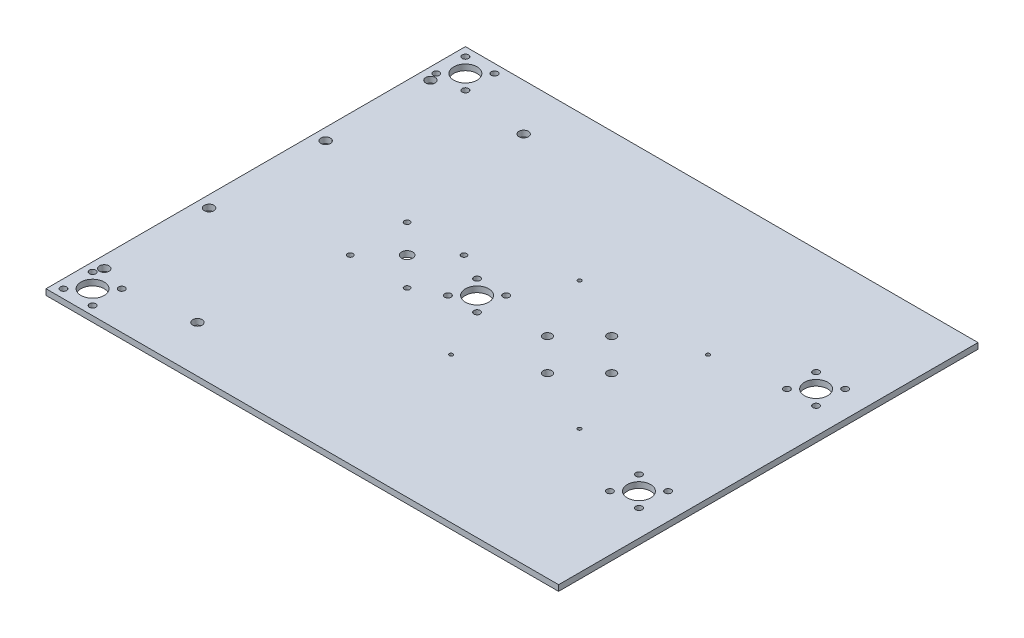
SolidWorks part; units mm, degrees
ref_plane "Front Plane" through (0, 0, 0) normal (0, 0, 1) x (1, 0, 0)
ref_plane "Top Plane" through (0, 0, 0) normal (0, 1, 0) x (1, 0, 0)
ref_plane "Right Plane" through (0, 0, 0) normal (1, 0, 0) x (0, 0, -1)
sketch "Sketch1" plane through (0, 0, 0) normal (0, 1, 0) x (1, 0, 0)
  line L1 (-139.7, -114.3) -> (139.7, -114.3)
  line L2 (-139.7, -114.3) -> (-139.7, 114.3)
  line L3 (-139.7, 114.3) -> (139.7, 114.3)
  line L4 (139.7, -114.3) -> (139.7, 114.3)
  line L5 (-139.7, -114.3) -> (139.7, 114.3) construction
  line L6 (-139.7, 114.3) -> (139.7, -114.3) construction
  point P0 (0, 0)
  dimension "D1" = 228.6
  dimension "D2" = 279.4
extrude "Boss-Extrude1" add sketch "Sketch1" along normal blind 3.175
sketch "Sketch2" plane through (0, 0, 0) normal (0, 1, 0) x (1, 0, 0)
  line L0 (-193.2668, 0) -> (192.9727, 0) construction
sketch "Sketch3" plane through (0, 3.175, 0) normal (0, 1, 0) x (1, 0, 0)
  circle A1 centre (-133.35, -31.75) radius 2.6
  circle A2 centre (-133.35, -31.75) radius 2.6
  circle A3 centre (-82.55, -88.9) radius 2.6
  circle A4 centre (-82.55, -88.9) radius 2.6
  circle A5 centre (-133.35, -88.9) radius 2.6
  circle A6 centre (-133.35, -88.9) radius 2.6
  dimension "D1" = 0
  dimension "D2" = 0
  dimension "D3" = 0
sketch "Sketch5" plane through (0, 3.175, 0) normal (0, 1, 0) x (1, 0, 0)
  circle A0 centre (-41.674, 15.5) radius 1.5 construction
  circle A1 centre (-41.674, -15.5) radius 1.5 construction
  circle A2 centre (-72.674, 15.5) radius 1.5 construction
  circle A3 centre (-72.674, -15.5) radius 1.5 construction
  circle A4 centre (-57.174, 0) radius 2.5 construction
  circle A5 centre (-41.674, 15.5) radius 1.5
  circle A6 centre (-41.674, -15.5) radius 1.5
  circle A7 centre (-72.674, 15.5) radius 1.5
  circle A8 centre (-72.674, -15.5) radius 1.5
  circle A9 centre (-57.174, 0) radius 2.5 construction
  circle A10 centre (-57.174, 0) radius 3.008
  dimension "D1" = 6.016
sketch "Sketch7" plane through (0, 3.175, 0) normal (0, 1, 0) x (1, 0, 0)
  circle A0 centre (71.8318, -35.0018) radius 1 construction
  circle A1 centre (1.8282, -35.0018) radius 1 construction
  circle A2 centre (71.8318, -35.0018) radius 1
  circle A3 centre (1.8282, -35.0018) radius 1
  circle A4 centre (1.8282, 35.0018) radius 1 construction
  circle A5 centre (71.8318, 35.0018) radius 1 construction
  circle A6 centre (1.8282, 35.0018) radius 1
  circle A7 centre (71.8318, 35.0018) radius 1
extrude "Cut-Extrude1" cut sketch "Sketch3" against normal through all
mirror "Mirror1" about plane through (0, 0, 0) normal (0, 0, 1) of "Cut-Extrude1"
extrude "Cut-Extrude2" cut sketch "Sketch5" against normal through all
extrude "Cut-Extrude3" cut sketch "Sketch7" against normal through all
sketch "Sketch8" plane through (0, 3.175, 0) normal (0, 1, 0) x (1, 0, 0)
  arc A0 (36.83, -19.85) -> (36.83, -15.15) centre (36.83, -17.5) ccw construction
  arc A1 (36.83, -19.85) -> (36.83, -15.15) centre (36.83, -17.5) ccw
  arc A2 (36.83, -15.15) -> (36.83, -19.85) centre (36.83, -17.5) ccw construction
  arc A3 (36.83, -15.15) -> (36.83, -19.85) centre (36.83, -17.5) ccw
  circle A4 centre (19.33, 0) radius 2.35 construction
  circle A5 centre (19.33, 0) radius 2.35
  arc A6 (36.83, 15.15) -> (36.83, 19.85) centre (36.83, 17.5) ccw construction
  arc A7 (36.83, 15.15) -> (36.83, 19.85) centre (36.83, 17.5) ccw
  arc A8 (36.83, 19.85) -> (36.83, 15.15) centre (36.83, 17.5) ccw construction
  arc A9 (36.83, 19.85) -> (36.83, 15.15) centre (36.83, 17.5) ccw
  circle A10 centre (54.33, 0) radius 2.35 construction
  circle A11 centre (54.33, 0) radius 2.35
extrude "Cut-Extrude4" cut sketch "Sketch8" against normal through all
sketch "Sketch9" plane through (0, 3.175, 0) normal (0, 1, 0) x (1, 0, 0)
  circle A0 centre (-119.0625, -109.5375) radius 1.727 construction
  circle A1 centre (-119.0625, -93.6625) radius 1.727 construction
  circle A2 centre (-134.9375, -93.6625) radius 1.727 construction
  circle A3 centre (-134.9375, -109.5375) radius 1.727 construction
  circle A4 centre (-127, -101.6) radius 6.35 construction
  circle A5 centre (-119.0625, -109.5375) radius 1.727
  circle A6 centre (-119.0625, -93.6625) radius 1.727
  circle A7 centre (-134.9375, -93.6625) radius 1.727
  circle A8 centre (-134.9375, -109.5375) radius 1.727
  circle A9 centre (-127, -101.6) radius 6.35
  circle A10 centre (125.4125, -56.1975) radius 1.727 construction
  circle A11 centre (125.4125, -40.3225) radius 1.727 construction
  circle A12 centre (117.475, -48.26) radius 6.35 construction
  circle A13 centre (109.5375, -40.3225) radius 1.727 construction
  circle A14 centre (109.5375, -56.1975) radius 1.727 construction
  circle A15 centre (125.4125, -56.1975) radius 1.727
  circle A16 centre (125.4125, -40.3225) radius 1.727
  circle A17 centre (117.475, -48.26) radius 6.35
  circle A18 centre (109.5375, -40.3225) radius 1.727
  circle A19 centre (109.5375, -56.1975) radius 1.727
  circle A20 centre (-11.1125, 7.9375) radius 1.727 construction
  circle A21 centre (-11.1125, -7.9375) radius 1.727 construction
  circle A22 centre (-19.05, 0) radius 6.35 construction
  circle A23 centre (-26.9875, -7.9375) radius 1.727 construction
  circle A24 centre (-26.9875, 7.9375) radius 1.727 construction
  circle A25 centre (-11.1125, 7.9375) radius 1.727
  circle A26 centre (-11.1125, -7.9375) radius 1.727
  circle A27 centre (-19.05, 0) radius 6.35
  circle A28 centre (-26.9875, -7.9375) radius 1.727
  circle A29 centre (-26.9875, 7.9375) radius 1.727
  circle A30 centre (109.5375, 56.1975) radius 1.727 construction
  circle A31 centre (109.5375, 40.3225) radius 1.727 construction
  circle A32 centre (125.4125, 56.1975) radius 1.727 construction
  circle A33 centre (117.475, 48.26) radius 6.35 construction
  circle A34 centre (125.4125, 40.3225) radius 1.727 construction
  circle A35 centre (109.5375, 56.1975) radius 1.727
  circle A36 centre (109.5375, 40.3225) radius 1.727
  circle A37 centre (125.4125, 56.1975) radius 1.727
  circle A38 centre (117.475, 48.26) radius 6.35
  circle A39 centre (125.4125, 40.3225) radius 1.727
  circle A40 centre (-119.0625, 93.6625) radius 1.727 construction
  circle A41 centre (-119.0625, 109.5375) radius 1.727 construction
  circle A42 centre (-134.9375, 109.5375) radius 1.727 construction
  circle A43 centre (-134.9375, 93.6625) radius 1.727 construction
  circle A44 centre (-119.0625, 93.6625) radius 1.727
  circle A45 centre (-119.0625, 109.5375) radius 1.727
  circle A46 centre (-134.9375, 109.5375) radius 1.727
  circle A47 centre (-134.9375, 93.6625) radius 1.727
  circle A48 centre (-127, 101.6) radius 6.35 construction
  circle A49 centre (-127, 101.6) radius 6.35
extrude "Cut-Extrude5" cut sketch "Sketch9" against normal through all both and the other way through all
equation "\"tightTol\"= 0.005in"
equation "\"normTol\"= 0.01in"
equation "\"looseTol\"= 0.02in"
equation "\"D1@Sketch5\"=5mm+2*\"looseTol\""
